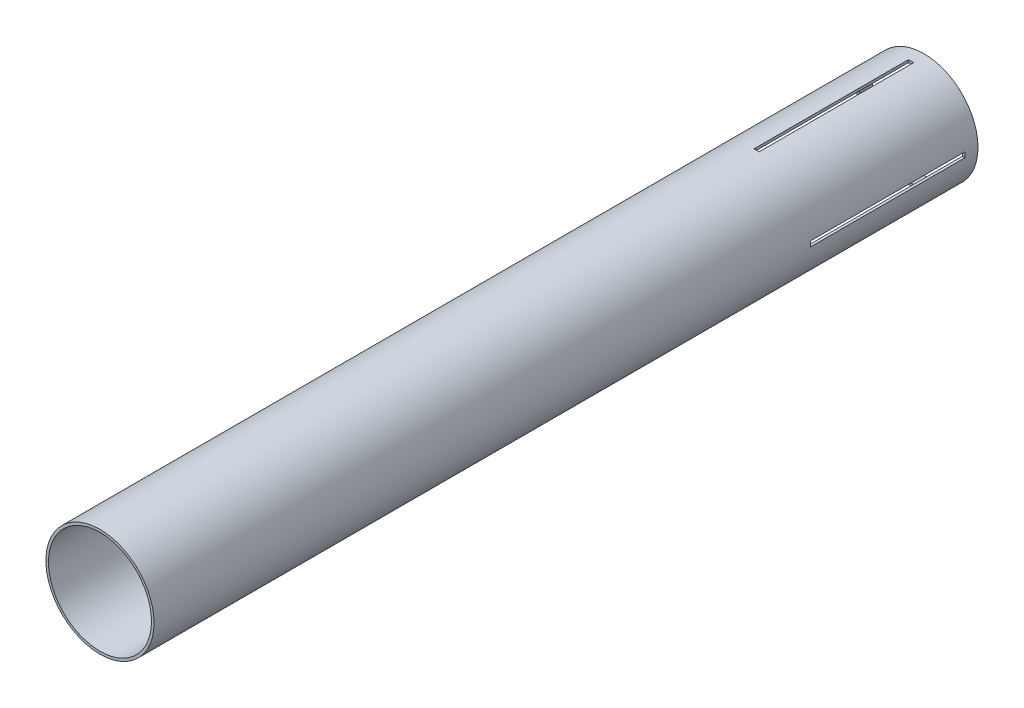
SolidWorks part; units mm, degrees
material "Corrugated Paper"
ref_plane "Front Plane" through (0, 0, 0) normal (0, 0, 1) x (1, 0, 0)
ref_plane "Top Plane" through (0, 0, 0) normal (0, 1, 0) x (1, 0, 0)
ref_plane "Right Plane" through (0, 0, 0) normal (1, 0, 0) x (0, 0, -1)
sketch "Sketch1" plane through (0, 0, 0) normal (0, 0, 1) x (1, 0, 0)
  circle A0 centre (0, 0) radius 50.8
  circle A1 centre (0, 0) radius 53.34
  dimension "D1" = 101.6
  dimension "D2" = 106.68
extrude "Boss-Extrude1" add sketch "Sketch1" along normal blind 812.8
sketch "Sketch2" plane through (0, 0, 0) normal (1, 0, 0) x (0, 0, -1)
  line L0 (0, -53.34) -> (0, 53.34) construction
  line L1 (-165.1, -2.54) -> (-12.7, -2.54)
  line L2 (-165.1, -2.54) -> (-165.1, 2.54)
  line L3 (-165.1, 2.54) -> (-12.7, 2.54)
  line L4 (-12.7, -2.54) -> (-12.7, 2.54)
  line L5 (-165.1, -2.54) -> (-12.7, 2.54) construction
  line L6 (-165.1, 2.54) -> (-12.7, -2.54) construction
  point P0 (-88.9, 0)
  point P7 (0, 0)
  dimension "D1" = 5.08
  dimension "D2" = 152.4
  dimension "D3" = 12.7
extrude "Cut-Extrude1" cut sketch "Sketch2" against normal up to next
ref_axis "Axis1" through (0, 0, -40.64) along (0, 0, 1)
pattern_circular "CirPattern1" count 4 every 90 about axis through (0, 0, -40.64) along (0, 0, 1) of "Cut-Extrude1"
